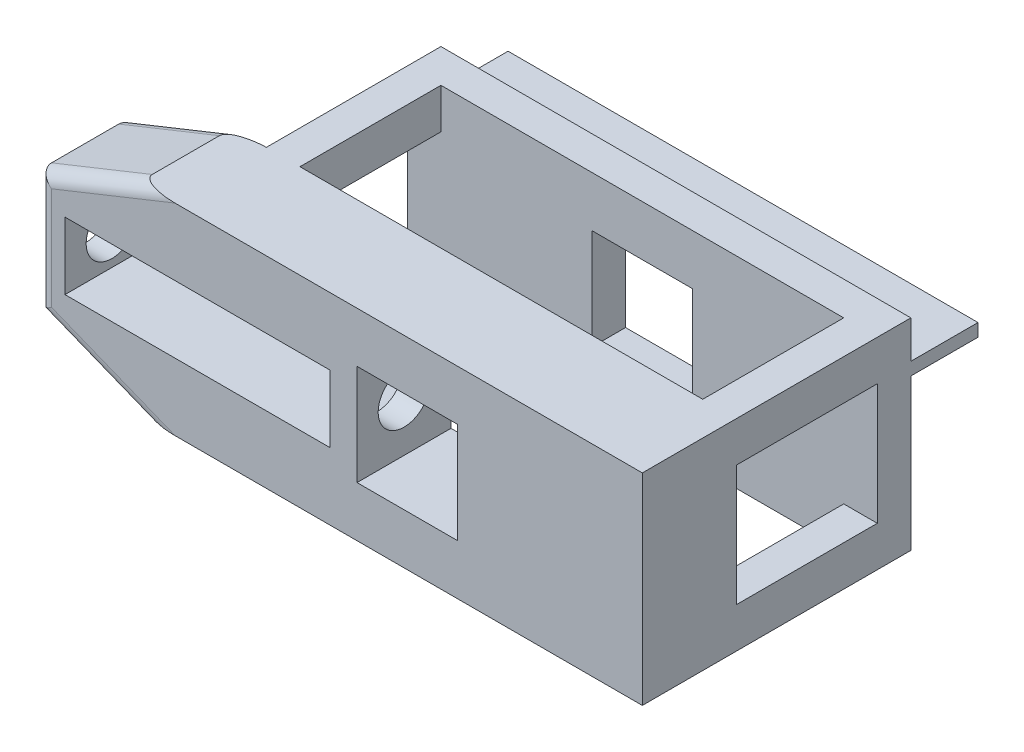
SolidWorks part; units mm, degrees
other "Markup1"
sketch "Sketch12" plane through (0, 38.1, 0) normal (-0.0705, 0.1614, 0.9844) x (0.9933, -0.0793, 0.0841)
material "ABS"
ref_plane "Front Plane" through (0, 0, 0) normal (0, 0, 1) x (1, 0, 0)
ref_plane "Top Plane" through (0, 0, 0) normal (0, 1, 0) x (1, 0, 0)
ref_plane "Right Plane" through (0, 0, 0) normal (1, 0, 0) x (0, 0, -1)
sketch "Sketch1" plane through (0, 0, 0) normal (0, 0, 1) x (1, 0, 0)
  line L1 (0, 0) -> (88.9, 0)
  line L2 (0, 0) -> (0, 38.1)
  line L3 (0, 38.1) -> (88.9, 38.1)
  line L4 (88.9, 0) -> (88.9, 38.1)
  line L5 (0, 0) -> (-25.4, 0)
  line L6 (0, 0) -> (0, 38.1)
  line L7 (0, 38.1) -> (-25.4, 38.1)
  line L8 (-25.4, 0) -> (-25.4, 38.1)
  dimension "D1" = 88.9
  dimension "D2" = 38.1
extrude "Boss-Extrude1" add sketch "Sketch1" against normal blind 17.78 contours L1 L4 L3 L2 | L8 L5 L2 L7 region at (44.45, 19.05, 0) region at (-12.7, 19.05, 0)
sketch "Sketch2" plane through (0, 0, 0) normal (0, 0, 1) x (1, 0, 0)
  line L0 (0, 19.05) -> (88.9, 19.05) construction
  line L1 (0, 0) -> (0, 38.1) construction
  line L2 (88.9, 0) -> (88.9, 38.1) construction
  line L3 (44.45, 0) -> (44.45, 38.1) construction
  line L4 (0, 0) -> (88.9, 0) construction
  line L5 (0, 38.1) -> (88.9, 38.1) construction
  line L6 (88.9, 30.48) -> (82.55, 30.48)
  line L7 (34.925, 28.575) -> (53.975, 28.575)
  line L8 (34.925, 28.575) -> (34.925, 9.525)
  line L9 (34.925, 9.525) -> (53.975, 9.525)
  line L10 (53.975, 28.575) -> (53.975, 9.525)
  line L11 (0, 38.1) -> (6.35, 38.1)
  line L12 (0, 38.1) -> (0, 30.48)
  line L13 (0, 30.48) -> (6.35, 30.48)
  line L14 (6.35, 38.1) -> (6.35, 30.48)
  line L15 (82.55, 38.1) -> (82.55, 30.48)
  line L16 (88.9, 38.1) -> (82.55, 38.1)
  line L17 (88.9, 38.1) -> (88.9, 30.48)
  line L18 (88.9, 0) -> (88.9, 7.62)
  line L19 (88.9, 0) -> (82.55, 0)
  line L20 (82.55, 0) -> (82.55, 7.62)
  line L21 (88.9, 7.62) -> (82.55, 7.62)
  line L22 (0, 7.62) -> (6.35, 7.62)
  line L23 (6.35, 0) -> (6.35, 7.62)
  line L24 (0, 0) -> (6.35, 0)
  line L25 (0, 0) -> (0, 7.62)
  line L26 (-25.4, 0) -> (-25.4, 38.1) construction
  line L27 (29.845, 25.4) -> (-8.255, 25.4)
  line L28 (29.845, 25.4) -> (29.845, 12.7)
  line L29 (29.845, 12.7) -> (-8.255, 12.7)
  line L30 (-8.255, 25.4) -> (-8.255, 12.7)
  line L31 (-25.4, 38.1) -> (88.9, 38.1) construction
  line L32 (-8.255, 25.4) -> (-20.32, 25.4)
  line L33 (-8.255, 25.4) -> (-8.255, 12.7)
  line L34 (-8.255, 12.7) -> (-20.32, 12.7)
  line L35 (-20.32, 25.4) -> (-20.32, 12.7)
  dimension "D1" = 19.05
  dimension "D3" = 34.925
  dimension "D7" = 6.35
  dimension "D10" = 12.7
  dimension "D2" = 19.05
  dimension "D4" = 9.525
  dimension "D11" = 6.35
  dimension "D8" = 5.08
  dimension "D9" = 38.1
  dimension "D5" = 7.62
  dimension "D6" = 5.08
extrude "Cut-Extrude1" cut sketch "Sketch2" against normal blind 41.402 contours L27 L30 L29 L28 | L14 L11 L12 L13 | L25 L24 L23 L22 | L10 L7 L8 L9 | L17 L16 L15 L6 | L18 L21 L20 L19 | L33 L32 L35 L34 region at (85.725, 34.29, 0) region at (44.45, 19.05, 0) region at (3.175, 34.29, 0) region at (85.725, 3.81, 0) region at (3.175, 3.81, 0) region at (10.795, 19.05, 0)
ref_plane "Plane1" through (0, 0, -50.8) normal (0, 0, 1) x (1, 0, 0)
sketch "Sketch3" plane through (0, 0, -50.8) normal (0, 0, 1) x (1, 0, 0)
  line L4 (34.925, 9.525) -> (53.975, 9.525)
  line L5 (53.975, 9.525) -> (53.975, 28.575)
  line L6 (53.975, 28.575) -> (34.925, 28.575)
  line L7 (34.925, 28.575) -> (34.925, 9.525)
  line L8 (0, 0) -> (0, 38.1)
  line L94 (88.9, 30.48) -> (82.55, 30.48)
  line L96 (88.9, 7.62) -> (88.9, 30.48)
  line L98 (82.55, 7.62) -> (88.9, 7.62)
  line L104 (82.55, 0) -> (82.55, 7.62)
  line L105 (6.35, 0) -> (82.55, 0)
  line L106 (6.35, 7.62) -> (6.35, 0)
  line L107 (0, 7.62) -> (6.35, 7.62)
  line L108 (0, 0) -> (0, 7.62)
  line L109 (-25.4, 0) -> (0, 0)
  line L110 (-25.4, 38.1) -> (-25.4, 0)
  line L111 (0, 38.1) -> (-25.4, 38.1)
  line L112 (0, 30.48) -> (0, 38.1)
  line L113 (6.35, 30.48) -> (0, 30.48)
  line L114 (6.35, 38.1) -> (6.35, 30.48)
  line L115 (82.55, 38.1) -> (6.35, 38.1)
  line L116 (82.55, 30.48) -> (82.55, 38.1)
  line L117 (88.9, 30.48) -> (82.55, 30.48)
  line L118 (88.9, 7.62) -> (88.9, 30.48)
  line L119 (82.55, 7.62) -> (88.9, 7.62)
  line L120 (82.55, 0) -> (82.55, 7.62)
  line L121 (6.35, 0) -> (82.55, 0)
  line L122 (6.35, 7.62) -> (6.35, 0)
  line L123 (0, 7.62) -> (6.35, 7.62)
  line L124 (0, 0) -> (0, 7.62)
  line L125 (-25.4, 0) -> (0, 0)
  line L126 (-25.4, 38.1) -> (-25.4, 0)
  line L127 (0, 38.1) -> (-25.4, 38.1)
  line L128 (0, 30.48) -> (0, 38.1)
  line L129 (6.35, 30.48) -> (0, 30.48)
  line L130 (6.35, 38.1) -> (6.35, 30.48)
  line L131 (82.55, 38.1) -> (6.35, 38.1)
  line L132 (82.55, 30.48) -> (82.55, 38.1)
  dimension "D2" = 9.525
  dimension "D3" = 9.525
  dimension "D4" = 19.05
  dimension "D5" = 28.575
  dimension "D6" = 19.05
  dimension "D1" = 0
extrude "Boss-Extrude2" add sketch "Sketch3" along normal blind 6.35 contours L117 L132 L131 L130 L129 L8 L123 L122 L121 L120 L119 L118 L7 L6 L5 L4 region at (0.9672, 19.05, -50.8)
sketch "Sketch6" plane through (-25.4, 0, 0) normal (-1, 0, 0) x (0, 0, 1)
  line L5 (-17.78, 25.4) -> (-17.78, 12.7)
  line L6 (-17.78, 12.7) -> (0, 12.7)
  line L7 (-17.78, 25.4) -> (-17.78, 12.7)
  line L8 (0, 25.4) -> (-17.78, 25.4)
  line L9 (0, 12.7) -> (0, 25.4)
  line L10 (-17.78, 12.7) -> (0, 12.7)
  line L12 (0, 25.4) -> (-17.78, 25.4)
  line L14 (0, 12.7) -> (0, 25.4)
  circle A0 centre (-8.89, 19.05) radius 4.8895
  dimension "D2" = 9.779
  dimension "D5" = 12.7
  dimension "D3" = 6.35
  dimension "D1" = 8.89
extrude "SpringPlunger Hole" cut sketch "Sketch6" against normal up to surface (60.325 mm away) contours A0 up to face at (34.925, 19.05, -8.89)
sketch "Sketch8" plane through (0, 0, 0) normal (0, 0, 1) x (1, 0, 0)
  line L30 (0, 0) -> (0, 38.1) construction
  line L31 (0, 38.1) -> (6.35, 38.1)
  line L32 (0, 38.1) -> (0, 30.1625)
  line L33 (0, 30.1625) -> (6.35, 30.1625)
  line L34 (6.35, 38.1) -> (6.35, 30.1625)
  line L35 (82.55, 38.1) -> (88.9, 38.1)
  line L36 (82.55, 38.1) -> (82.55, 30.1625)
  line L37 (82.55, 30.1625) -> (88.9, 30.1625)
  line L38 (88.9, 38.1) -> (88.9, 30.1625)
  line L39 (82.55, 7.9375) -> (88.9, 7.9375)
  line L40 (82.55, 7.9375) -> (82.55, 0)
  line L41 (82.55, 0) -> (88.9, 0)
  line L42 (88.9, 7.9375) -> (88.9, 0)
  line L43 (0, 7.9375) -> (6.35, 7.9375)
  line L44 (0, 7.9375) -> (0, 0)
  line L45 (0, 0) -> (6.35, 0)
  line L46 (6.35, 7.9375) -> (6.35, 0)
  line L48 (0, 0) -> (88.9, 0) construction
extrude "Support" add sketch "Sketch8" against normal up to surface (50.8 mm away) up to face at (44.45, 19.05, -50.8)
sketch "Sketch9" plane through (29.845, 0, 0) normal (-1, 0, 0) x (0, 0, 1)
  circle A3 centre (-8.89, 19.05) radius 4.8895
  dimension "D2" = 9.779
extrude "Cut-Extrude4" [suppressed] cut sketch "Sketch9" against normal up to surface (5.08 mm away) up to face at (34.925, 19.05, -4.0005)
sketch "Sketch10" plane through (0, 0, -50.8) normal (0, 0, -1) x (-1, 0, 0)
  line L1 (-88.9, 30.988) -> (0, 30.988)
  line L2 (-88.9, 30.988) -> (-88.9, 28.575)
  line L3 (-88.9, 28.575) -> (0, 28.575)
  line L4 (0, 30.988) -> (0, 28.575)
  line L8 (-88.9, 38.1) -> (0, 38.1) construction
  line L10 (-88.9, 0) -> (-88.9, 38.1) construction
  dimension "D1" = 7.112
  dimension "D2" = 88.9
  dimension "D3" = 2.413
extrude "Boss-Extrude3" add sketch "Sketch10" along normal blind 12.7
sketch "Sketch11" [suppressed] plane through (0, 0, 0) normal (0, 0, 1) x (1, 0, 0)
  line L0 (88.9, 0) -> (88.9, 38.1) construction
  line L1 (60.325, 27.94) -> (82.55, 27.94)
  line L2 (60.325, 27.94) -> (60.325, 6.35)
  line L3 (60.325, 6.35) -> (82.55, 6.35)
  line L4 (82.55, 27.94) -> (82.55, 6.35)
  line L5 (53.975, 28.575) -> (53.975, 9.525) construction
  line L6 (0, 38.1) -> (88.9, 38.1) construction
  line L7 (0, 0) -> (88.9, 0) construction
  dimension "D1" = 6.35
  dimension "D2" = 6.35
  dimension "D3" = 10.16
  dimension "D4" = 6.35
sketch "Sketch13" plane through (0, 0, 0) normal (0, 0, 1) x (1, 0, 0)
  line L0 (-6.35, 38.1) -> (-25.4, 30.48)
  line L1 (-25.4, 0) -> (-25.4, 38.1) construction
  line L2 (-6.35, 38.1) -> (-25.4, 38.1)
  line L3 (-25.4, 38.1) -> (-25.4, 30.48)
  line L4 (-6.35, 0) -> (-25.4, 0)
  line L5 (-25.4, 0) -> (-25.4, 7.62)
  line L6 (-25.4, 7.62) -> (-6.35, 0)
  line L7 (-25.4, 0) -> (88.9, 0) construction
  point P11 (0, 38.1)
  point P13 (-5.2489, 38.1)
  point P14 (-3.5151, 0)
  line M4 (88.9, 38.1) -> (-25.4, 38.1)
  line M5 (-25.4, 38.1) -> (-25.4, 0)
  line M6 (-25.4, 0) -> (88.9, 0)
  dimension "D1" = 7.62
  dimension "D2" = 7.62
  dimension "D3" = 6.35
  dimension "D4" = 6.35
extrude "Cut-Extrude5" cut sketch "Sketch13" against normal up to surface (17.78 mm away) contours L0 M4 M5 | L6 M5 M6 region at (-19.05, 2.54, 0) region at (-19.05, 35.56, 0) up to face at (44.45, 19.05, -17.78)
fillet "Fillet1" radius 2.54 6 edges at (-15.875, 3.81, 0) (-15.875, 3.81, -17.78) (-15.875, 34.29, -17.78) (-15.875, 34.29, 0) (-25.4, 19.05, 0) (-25.4, 19.05, -17.78)
equation "\"box\"= 3.5"
equation "\"D1@Sketch1\"=\"box\""
equation "\"shaft\"= .75"
equation "\"D1@Sketch2\"=\"shaft\""
equation "\"D3@Sketch2\"=(\"box\"-\"shaft\")/2"
equation "\"D7@Sketch2\"=0.25"
equation "\"springHole\"=1"
equation "\"depth1\"=0.7"
equation "\"D1@Boss-Extrude1\"=\"depth1\""
equation "\"springShaftD\"=0.385"
equation "\"D2@Sketch6\"=\"springShaftD\""
equation "\"D2@Sketch1\"=(\"box\"/3.5)*1.5"
equation "\"D2@Sketch2\"=\"shaft\""
equation "\"D4@Sketch2\"=\"shaft\"/2"
equation "\"D11@Sketch2\"=\"D10@Sketch2\"/2"
equation "\"D3@Sketch6\"=\"D5@Sketch6\"/2"
equation "\"springPinD\"=0.385"
equation "\"D2@Sketch9\"=\"springPinD\""
